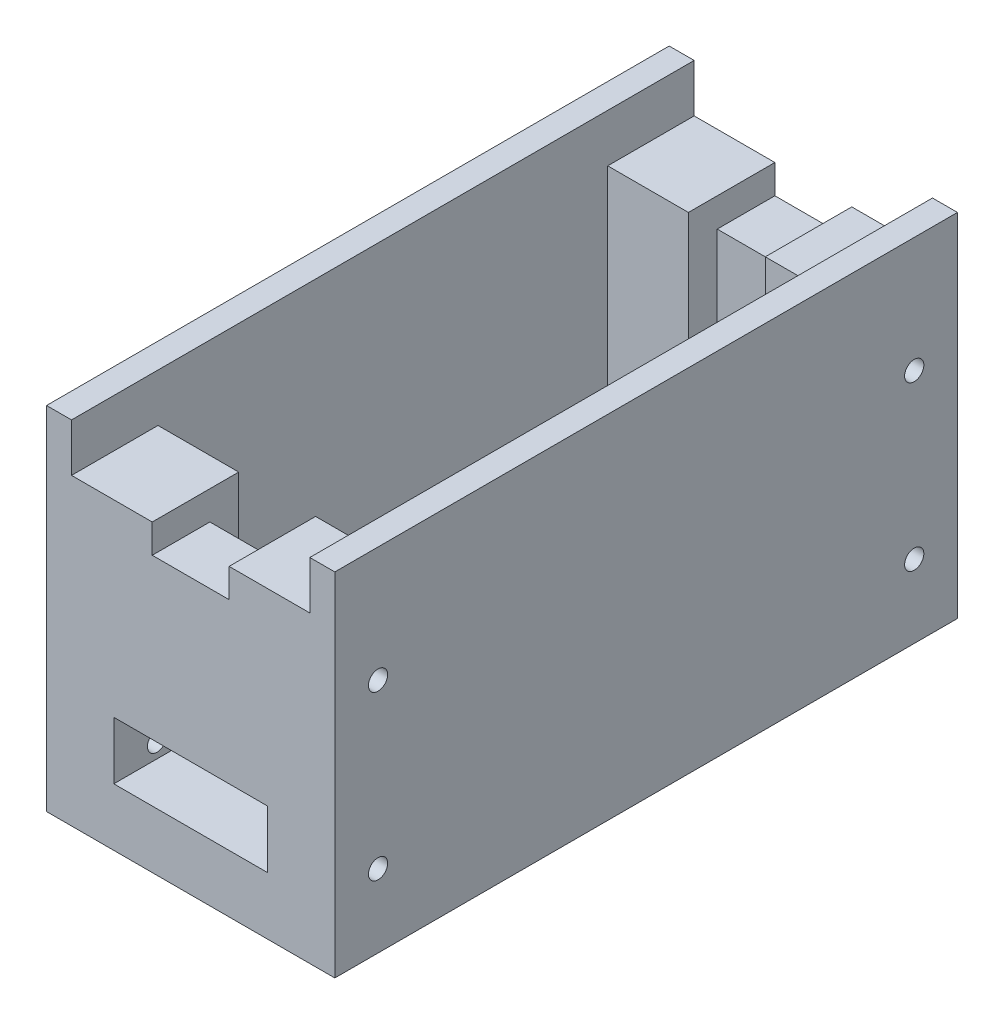
SolidWorks part; units mm, degrees
ref_plane "前视基准面" through (0, 0, 0) normal (0, 0, 1) x (1, 0, 0)
ref_plane "上视基准面" through (0, 0, 0) normal (0, 1, 0) x (1, 0, 0)
ref_plane "右视基准面" through (0, 0, 0) normal (1, 0, 0) x (0, 0, -1)
other "Configuration Table"
sketch "草图1" plane through (0, 0, 0) normal (0, 1, 0) x (1, 0, 0)
  line L1 (0, 0) -> (15, 0)
  line L2 (0, 0) -> (0, -32.4)
  line L3 (0, -32.4) -> (15, -32.4)
  line L4 (15, 0) -> (15, -32.4)
  circle A4 centre (3, -3) radius 0.8
  circle A5 centre (12, -3) radius 0.8
  circle A6 centre (3, -29.4) radius 0.8
  circle A7 centre (12, -29.4) radius 0.8
  circle A8 centre (7.5, -21.35) radius 6.25
  circle A9 centre (7.5, -15.6) radius 3
  point P10 (7.5, -32.4)
  dimension "D3" = 1.6
  dimension "D6" = 12.5
  dimension "D7" = 6
  dimension "D1" = 3
  dimension "D2" = 15
  dimension "D4" = 11.05
  dimension "D5" = 5.75
  dimension "D9" = 3
  dimension "D10" = 3
  dimension "D11" = 3
  dimension "32.4" = 32.4
extrude "凸台-拉伸1" add sketch "草图1" along normal blind 2.2 contours L2 L3 L4 L1 | A7 | A6 | A4 | A5
sketch "草图2" plane through (0, 2.2, 0) normal (0, 1, 0) x (1, 0, 0)
  line L0 (0, 0) -> (0, -32.4) construction
  line L1 (15, -32.4) -> (0, -32.4)
  line L2 (15, -32.4) -> (15, -27.9)
  line L3 (15, -27.9) -> (0, -27.9)
  line L4 (0, -32.4) -> (0, -27.9)
  line L6 (15, 0) -> (0, 0)
  line L7 (15, 0) -> (15, -4.5)
  line L8 (15, -4.5) -> (0, -4.5)
  line L9 (0, 0) -> (0, -4.5)
  line L10 (15, -32.4) -> (13.7, -32.4)
  line L11 (15, -32.4) -> (15, 0)
  line L12 (15, 0) -> (13.7, 0)
  line L13 (13.7, -32.4) -> (13.7, 0)
  line L15 (0, 0) -> (1.3, 0)
  line L16 (0, 0) -> (0, -32.4)
  line L17 (0, -32.4) -> (1.3, -32.4)
  line L18 (1.3, 0) -> (1.3, -32.4)
  line M19 (15, 0) -> (0, 0)
  line M20 (0, 0) -> (0, -32.4)
  line M21 (0, -32.4) -> (15, -32.4)
  line M22 (15, -32.4) -> (15, 0)
  circle M23 centre (12, -29.4) radius 0.8
  circle M24 centre (3, -29.4) radius 0.8
  circle M25 centre (3, -3) radius 0.8
  circle M26 centre (12, -3) radius 0.8
  dimension "D1" = 4.5
  dimension "D2" = 1.3
  dimension "D3" = 1.3
extrude "凸台-拉伸2" add sketch "草图2" along normal blind 15.8 contours L6 L18 L8 L13 M25 M26 | L18 L8 M19 M20 | L13 L8 M22 M19 | L3 L18 L1 L13 M24 M23 | L18 L3 M20 M21 | L13 L1 L3 M22 | M25 | M26 | M24 | M23 | L13 L3 L8 M22 | L18 L8 L3 M20 region at (14.35, 2.2, 30.15) region at (7.5, 2.2, 30.2082) region at (14.35, 2.2, 16.2) region at (0.65, 2.2, 30.15) region at (14.35, 2.2, 2.25) region at (0.65, 2.2, 16.2) region at (7.5, 2.2, 2.1918) region at (0.65, 2.2, 2.25) region at (12, 2.2, 29.4) region at (3, 2.2, 29.4) region at (3, 2.2, 3) region at (12, 2.2, 3)
extrude "凸台-拉伸3" add sketch "草图2<3>" along normal blind 2.5 from surface contours L18 L8 M19 M20 | L18 L8 L3 M20 | L18 L3 M20 M21 | L13 L1 L3 M22 | L13 L3 L8 M22 | L13 L8 M22 M19 region at (14.35, 2.2, 30.15) region at (14.35, 2.2, 16.2) region at (0.65, 2.2, 30.15) region at (14.35, 2.2, 2.25) region at (0.65, 2.2, 16.2) region at (0.65, 2.2, 2.25) starting at face at (7.5, 18, 16.2)
sketch "草图2<3>" plane through (0, 2.2, 0) normal (0, 1, 0) x (1, 0, 0) same geometry as "草图2"
sketch "草图3" plane through (0, 0, 0) normal (0, 0, -1) x (-1, 0, 0)
  line L0 (-13.7, 18) -> (-1.3, 18) construction
  line L1 (-11.5, 5.2) -> (-3.5, 5.2)
  line L2 (-11.5, 5.2) -> (-11.5, 8.2)
  line L3 (-11.5, 8.2) -> (-3.5, 8.2)
  line L4 (-3.5, 5.2) -> (-3.5, 8.2)
  line L5 (0, 0) -> (-15, 0) construction
  line L6 (-11.5, 5.2) -> (-15, 5.2) construction
  line L7 (-15, 20.5) -> (-15, 0) construction
  line L8 (-3.5, 5.2) -> (0, 5.2) construction
  line L9 (0, 20.5) -> (0, 0) construction
  line L10 (-9.5, 18) -> (-5.5, 18)
  line L11 (-9.5, 18) -> (-9.5, 16.5)
  line L12 (-9.5, 16.5) -> (-5.5, 16.5)
  line L13 (-5.5, 18) -> (-5.5, 16.5)
  line L14 (-9.5, 16.5) -> (-15, 16.5) construction
  line L15 (-5.5, 16.5) -> (0, 16.5) construction
  dimension "D1" = 8
  dimension "D2" = 3
  dimension "D3" = 5.2
  dimension "D4" = 1.5
  dimension "D5" = 4
extrude "切除-拉伸1" cut sketch "草图3" against normal through all
sketch "草图4" plane through (15, 0, 0) normal (1, 0, 0) x (0, 0, -1)
  line L0 (-32.4, 20.5) -> (-32.4, 0) construction
  line L1 (0, 0) -> (-32.4, 0) construction
  line L2 (0, 20.5) -> (-32.4, 20.5) construction
  line L3 (0, 20.5) -> (0, 0) construction
  circle A0 centre (-30.15, 6) radius 0.5
  circle A1 centre (-2.25, 6) radius 0.5
  circle A2 centre (-30.15, 14.5) radius 0.5
  circle A3 centre (-2.25, 14.5) radius 0.5
  dimension "D5" = 1
  dimension "D1" = 2.25
  dimension "D2" = 6
  dimension "D3" = 6
  dimension "D4" = 2.25
extrude "切除-拉伸2" cut sketch "草图4" against normal through all contours A0 | A2 | A1 | A3
sketch "草图5" plane through (0, 0, 0) normal (-1, 0, 0) x (0, 0, 1)
  line L0 (32.4, 20.5) -> (32.4, 0) construction
  line L1 (0, 0) -> (32.4, 0)
  line L2 (0, 0) -> (0, 2.2)
  line L3 (0, 2.2) -> (32.4, 2.2)
  line L4 (32.4, 0) -> (32.4, 2.2)
  dimension "D1" = 2.2
extrude "切除-拉伸3" cut sketch "草图5" against normal through all
sketch "草图6" plane through (0, 2.2, 0) normal (0, -1, 0) x (1, 0, 0)
  line L0 (12, 32.4) -> (12, 27.9) construction
  line L1 (15, 32.4) -> (0, 32.4) construction
  line L2 (13.7, 27.9) -> (1.3, 27.9) construction
  line L3 (3, 4.5) -> (3, 0) construction
  line L4 (13.7, 4.5) -> (1.3, 4.5) construction
  line L5 (15, 0) -> (0, 0) construction
  line L6 (12, 30.15) -> (15, 30.15) construction
  line L7 (15, 32.4) -> (15, 0) construction
  line L8 (3, 2.25) -> (0, 2.25) construction
  line L9 (0, 32.4) -> (0, 0) construction
  circle A0 centre (12, 30.15) radius 0.5
  circle A1 centre (3, 30.15) radius 0.5
  circle A2 centre (12, 2.25) radius 0.5
  circle A3 centre (3, 2.25) radius 0.5
  dimension "D1" = 1
  dimension "D2" = 3
extrude "切除-拉伸4" cut sketch "草图6" against normal blind 2 contours A1 | A0 | A2 | A3
sketch "草图7" plane through (0, 16.5, 0) normal (0, 1, 0) x (1, 0, 0)
  line L0 (5.5, -27.9) -> (1.3, -27.9) construction
  line L1 (5.5, -27.9) -> (9.5, -27.9)
  line L2 (5.5, -27.9) -> (5.5, -29.4)
  line L3 (5.5, -29.4) -> (9.5, -29.4)
  line L4 (9.5, -27.9) -> (9.5, -29.4)
  line L5 (5.5, -29.4) -> (1.3, -29.4) construction
  line L6 (1.3, -32.4) -> (1.3, 0) construction
  line L7 (9.5, -29.4) -> (13.7, -29.4) construction
  line L8 (13.7, 0) -> (13.7, -32.4) construction
  line L9 (5.5, -4.5) -> (1.3, -4.5) construction
  line L10 (5.5, -4.5) -> (9.5, -4.5)
  line L11 (5.5, -4.5) -> (5.5, -3)
  line L12 (5.5, -3) -> (9.5, -3)
  line L13 (9.5, -4.5) -> (9.5, -3)
  dimension "D1" = 4
  dimension "D2" = 1.5
extrude "切除-拉伸5" cut sketch "草图7" against normal through all
